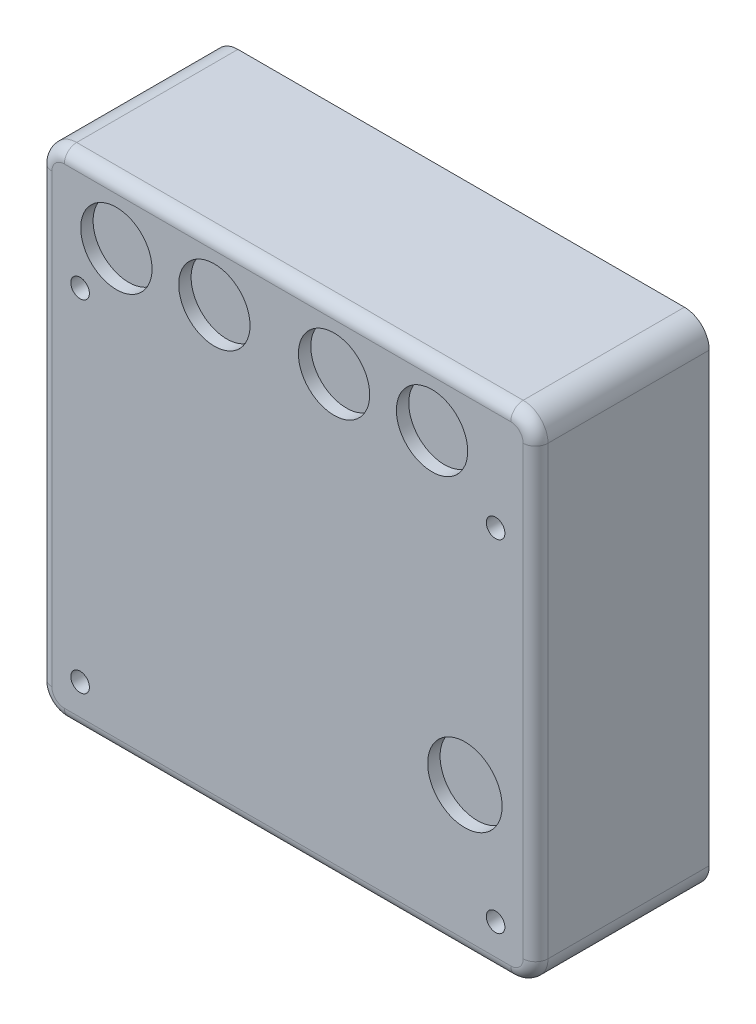
SolidWorks part; units mm, degrees
ref_plane "Front Plane" through (0, 0, 0) normal (0, 0, 1) x (1, 0, 0)
ref_plane "Top Plane" through (0, 0, 0) normal (0, 1, 0) x (1, 0, 0)
ref_plane "Right Plane" through (0, 0, 0) normal (1, 0, 0) x (0, 0, -1)
sketch "Sketch1" plane through (0, 0, 0) normal (0, 0, 1) x (1, 0, 0)
  line L1 (-40, 40) -> (40, 40)
  line L2 (-40, 40) -> (-40, -40)
  line L3 (-40, -40) -> (40, -40)
  line L4 (40, 40) -> (40, -40)
  line L5 (-40, 40) -> (40, -40) construction
  line L6 (-40, -40) -> (40, 40) construction
  point P0 (0, 0)
  dimension "D1" = 80
  dimension "D2" = 80
extrude "Boss-Extrude1" add sketch "Sketch1" along normal mid plane 28
fillet "Fillet1" radius 2 4 edges at (40, 0, 14) (0, -40, 14) (-40, 0, 14) (0, 40, 14)
fillet "Fillet2" radius 4 8 edges at (-39.4142, 39.4142, 13.4142) (39.4142, 39.4142, 13.4142) (-39.4142, -39.4142, 13.4142) (39.4142, -39.4142, 13.4142) (40, -40, -1) (-40, -40, -1) (40, 40, -1) (-40, 40, -1)
sketch "Sketch2" plane through (0, 0, 14) normal (0, 0, 1) x (1, 0, 0)
  line L0 (-27.6, 30.4) -> (-11.8, 30.4) construction
  line L1 (-11.8, 30.4) -> (7.5, 30.4) construction
  line L2 (7.5, 30.4) -> (23.3, 30.4) construction
  line L3 (-36, 40) -> (36, 40) construction
  line L4 (-40, -36) -> (-40, 36) construction
  circle A0 centre (-27.6, 30.4) radius 5.75
  circle A1 centre (-11.8, 30.4) radius 5.75
  circle A2 centre (7.5, 30.4) radius 5.75
  circle A3 centre (23.3, 30.4) radius 5.75
  dimension "D1" = 11.5
  dimension "D4" = 19.3
  dimension "D5" = 12.4
  dimension "D2" = 9.6
  dimension "D3" = 15.8
extrude "Cut-Extrude1" cut sketch "Sketch2" against normal blind 2
sketch "Sketch3" plane through (0, 0, 14) normal (0, 0, 1) x (1, 0, 0)
  line L1 (-33.45, 21.95) -> (33.55, 21.95) construction
  line L2 (-33.45, 21.95) -> (-33.45, -33.05) construction
  line L3 (-33.45, -33.05) -> (33.55, -33.05) construction
  line L4 (33.55, 21.95) -> (33.55, -33.05) construction
  circle A0 centre (-33.45, 21.95) radius 1.5
  circle A2 centre (33.55, 21.95) radius 1.5
  circle A3 centre (-33.45, -33.05) radius 1.5
  circle A4 centre (33.55, -33.05) radius 1.5
  circle A5 centre (23.3, 30.4) radius 5.75 construction
  circle A6 centre (23.3, 30.4) radius 5.75 construction
  dimension "D5" = 3
  dimension "D3" = 10.25
  dimension "D4" = 8.45
  dimension "D1" = 55
  dimension "D2" = 67
extrude "Cut-Extrude2" cut sketch "Sketch3" against normal blind 12
sketch "Sketch6" plane through (0, 0, 14) normal (0, 0, 1) x (1, 0, 0)
  circle A0 centre (28.6, -16.4) radius 6
  circle A1 centre (23.3, 30.4) radius 5.75 construction
  circle A2 centre (23.3, 30.4) radius 5.75 construction
  dimension "D1" = 12
  dimension "D2" = 5.3
  dimension "D3" = 46.8
extrude "Cut-Extrude3" cut sketch "Sketch6" against normal blind 2
sketch "Sketch7" plane through (0, 0, -14) normal (0, 0, -1) x (-1, 0, 0)
  line L1 (-16.75, 21) -> (16.75, 21)
  line L2 (-16.75, 21) -> (-16.75, -21)
  line L3 (-16.75, -21) -> (16.75, -21)
  line L4 (16.75, 21) -> (16.75, -21)
  line L5 (-16.75, 21) -> (16.75, -21) construction
  line L6 (-16.75, -21) -> (16.75, 21) construction
  point P0 (0, 0)
  dimension "D1" = 42
  dimension "D2" = 33.5
extrude "Boss-Extrude2" add sketch "Sketch7" along normal blind 2.5
